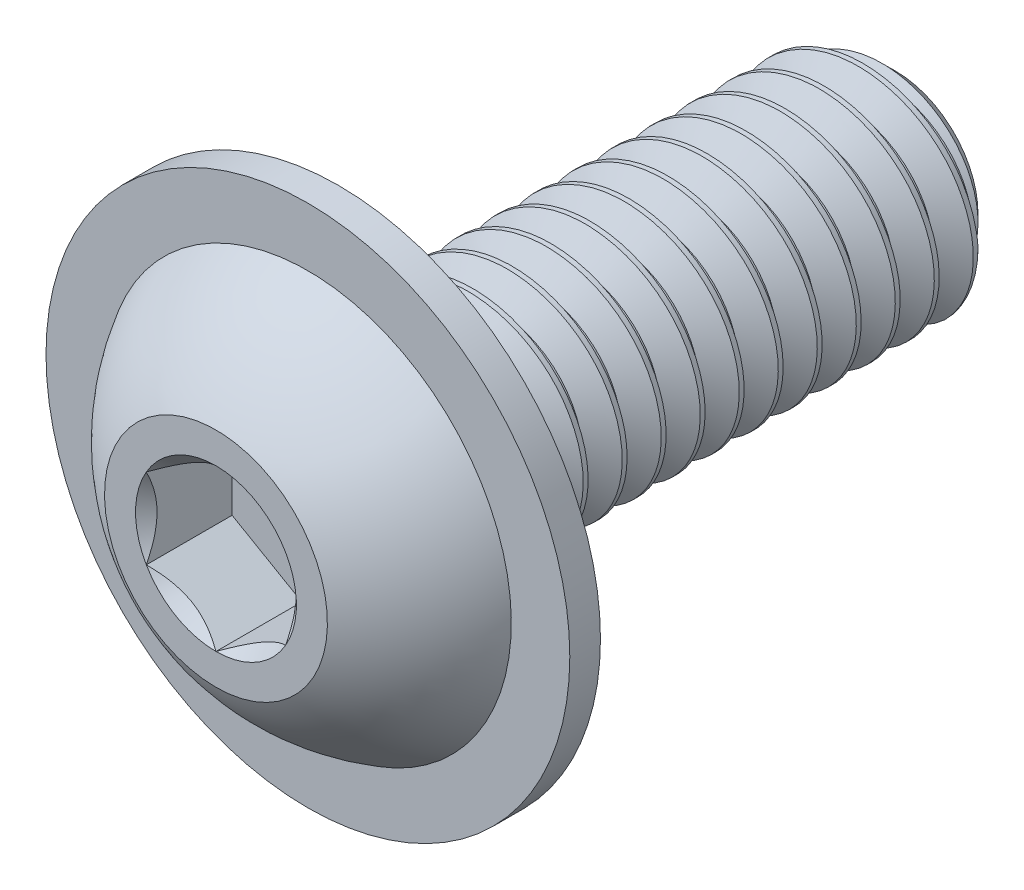
SolidWorks part; units mm, degrees
ref_plane "Front" through (0, 0, 0) normal (0, 0, 1) x (1, 0, 0)
ref_plane "Top" through (0, 0, 0) normal (0, 1, 0) x (1, 0, 0)
ref_plane "Right" through (0, 0, 0) normal (1, 0, 0) x (0, 0, -1)
sketch "Sketch1" plane through (0, 0, 0) normal (1, 0, 0) x (0, 0, -1)
  line L2 (2.2, 2) -> (12.2, 2)
  line L3 (12.2, 2) -> (12.2, 0)
  line L4 (12.2, 0) -> (2.2, 0)
  line L6 (1.65, 3.65) -> (2.2, 3.65) construction
  line L7 (12.2, 2) -> (12.2, -2) construction
  line L8 (0, 0) -> (2.2, 0) construction
  line L9 (2.2, 3.65) -> (2.2, -3.65) construction
  line L11 (2.2, 2) -> (2.2, 0)
  line L13 (0, 1.25) -> (0, -1.25) construction
  line L14 (0, 1.25) -> (0, 2) construction
  line L15 (1.65, 3.65) -> (1.65, 4.7) construction
  line L16 (1.65, 4.7) -> (2.2, 4.7) construction
  line L17 (2.2, 4.7) -> (2.2, 3.65) construction
  line L18 (2.2, 4.7) -> (2.2, -4.7) construction
  arc A3 (0, 2) -> (1.65, 3.65) centre (3.65, 0) cw construction
  dimension "D1" = 0.55
revolve "Revolve1" add sketch "Sketch1" angle 360 mid plane about L4
sketch "Sketch3" plane through (0, 0, -12.2) normal (0, 0, -1) x (-1, 0, 0)
  circle A0 centre (0, 0) radius 2
curve "Helix/Spiral1" pitch 0.7 height 10.7 radius 2 centre (0, 0, -12.2) axis (0, 0, 1) start towards (0, 1, 0)
sketch "Sketch2" plane through (0, 0, 0) normal (1, 0, 0) x (0, 0, -1)
  line L0 (12.2, 2) -> (12.8125, 2)
  line L1 (12.8125, 2) -> (12.55, 1.5453)
  line L2 (12.55, 1.5453) -> (12.4625, 1.5453)
  line L3 (12.4625, 1.5453) -> (12.2, 2)
  line L4 (12.3312, 1.7727) -> (12.6812, 1.7727) construction
  dimension "D1" = 60
  dimension "D2" = 0.0875
  dimension "D3" = 0.35
chamfer "Chamfer1" distance 0.525 angle 45 1 edges at (0, 2, -12.2)
sweep "Cut-Sweep1" cut profiles "Sketch2" path "Helix/Spiral1" align with end faces yes
sketch "Sketch7" plane through (0, 0, 0) normal (1, 0, 0) x (0, 0, -1)
  line L6 (1.65, 3.65) -> (2.2, 3.65) construction
  line L8 (0, 0) -> (2.2, 0) construction
  line L11 (2.2, 3.65) -> (2.2, -3.65) construction
  line L12 (1.65, 3.65) -> (2.2, 3.65)
  line L13 (0, 0) -> (2.2, 0)
  line L14 (0, 1.25) -> (0, -1.25) construction
  line L15 (2.2, 3.65) -> (2.2, 0)
  line L16 (0, 2) -> (0, 0)
  arc A2 (1.65, 3.65) -> (0, 2) centre (3.65, 0) ccw construction
  arc A3 (1.65, 3.65) -> (0, 2) centre (3.65, 0) ccw
revolve "Revolve2" add sketch "Sketch7" angle 360 mid plane about L13
sketch "Sketch11" plane through (0, 0, -2.2) normal (0, 0, -1) x (-1, 0, 0)
  circle A0 centre (0, 0) radius 4.7
extrude "Boss-Extrude3" add sketch "Sketch11" against normal up to vertex (0.55 mm away) up to point (0, 3.65, -1.65)
sketch "Sketch5" plane through (0, 0, 0) normal (0, 0, 1) x (1, 0, 0)
  line L1 (1.25, -0.7217) -> (1.25, 0.7217)
  line L2 (1.25, 0.7217) -> (0, 1.4434)
  line L3 (0, 1.4434) -> (-1.25, 0.7217)
  line L4 (-1.25, 0.7217) -> (-1.25, -0.7217)
  line L5 (-1.25, -0.7217) -> (0, -1.4434)
  line L6 (0, -1.4434) -> (1.25, -0.7217)
  circle A0 centre (0, 0) radius 1.25 construction
extrude "Cut-Extrude2" cut sketch "Sketch5" against normal blind 1.54
sketch "Sketch6" plane through (0, 0, 0) normal (0, 0, 1) x (1, 0, 0)
  circle A0 centre (0, 0) radius 1.4434
extrude "Cut-Extrude3" cut sketch "Sketch6" against normal blind 1.54 draft 45
sketch "Sketch9" [suppressed] plane through (0, 0, -5.0546) normal (0, 0, 1) x (1, 0, 0)
  circle A2 centre (0, 0) radius 4.7625
extrude "Boss-Extrude2" [suppressed] add sketch "Sketch9" against normal offset from surface (6.35 mm away) 31.75 up to face at (0, 1.475, -12.2)
sketch "Sketch10" plane through (0, 0, 0) normal (1, 0, 0) x (0, 0, -1)
  line L0 (12.2, 2) -> (12.2, -2) construction
  point P0 (11.15, -2)
  dimension "D1" = 1.05
equation "\"D3@Helix/Spiral1\" = \"Lg@Sketch1\" + \"D4@Helix/Spiral1\""
equation "\"D2@Sketch2\" = \"D4@Helix/Spiral1\" * .125"
equation "\"D3@Sketch2\" = \"D4@Helix/Spiral1\" * .5"
equation "\"D1@Chamfer1\" = \"D4@Helix/Spiral1\" * .75"
equation "\"D1@Cut-Extrude2\" = \"Head Ht@Sketch1\" * .7"
equation "\"D1@Sketch1\" = \"Head Ht@Sketch1\" * .25"
equation "\"D1@Sketch10\" = \"D4@Helix/Spiral1\" * 1.5"
equation "\"D1@Cut-Extrude3\" = \"D1@Cut-Extrude2\""
